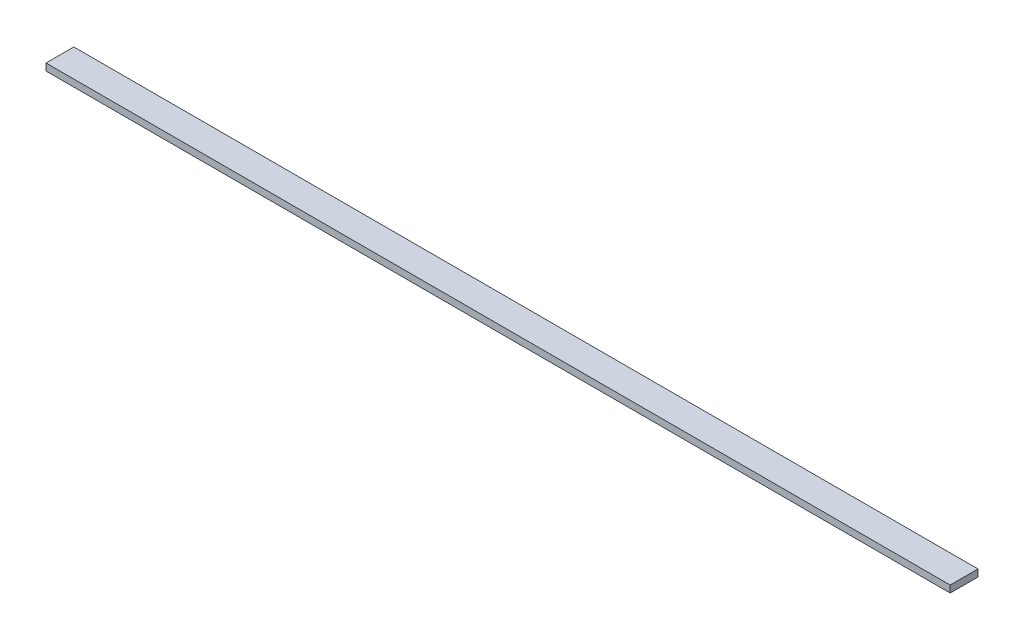
SolidWorks part; units mm, degrees
ref_plane "Front Plane" through (0, 0, 0) normal (0, 0, 1) x (1, 0, 0)
ref_plane "Top Plane" through (0, 0, 0) normal (0, 1, 0) x (1, 0, 0)
ref_plane "Right Plane" through (0, 0, 0) normal (1, 0, 0) x (0, 0, -1)
sketch "Sketch1" plane through (0, 0, 0) normal (0, 1, 0) x (1, 0, 0)
  line L1 (-412.75, -12.7) -> (412.75, -12.7)
  line L2 (-412.75, -12.7) -> (-412.75, 12.7)
  line L3 (-412.75, 12.7) -> (412.75, 12.7)
  line L4 (412.75, -12.7) -> (412.75, 12.7)
  line L5 (-412.75, -12.7) -> (412.75, 12.7) construction
  line L6 (-412.75, 12.7) -> (412.75, -12.7) construction
  point P0 (0, 0)
  dimension "D1" = 825.5
  dimension "D2" = 25.4
extrude "Boss-Extrude1" add sketch "Sketch1" along normal blind 6.35
equation "\"horizontal-component-length\"= \"railing-width\" - \"railing padding\""
equation "\"horizontal-component-width\"= 1in"
equation "\"D1@Sketch1\"=\"horizontal-component-length\""
equation "\"D2@Sketch1\"=\"horizontal-component-width\""
equation "\"material-thickness\"= .25in"
equation "\"D1@Boss-Extrude1\"=\"material-thickness\""
equation "\"railing-width\"= 33in"
equation "\"railing padding\"= .5in"
